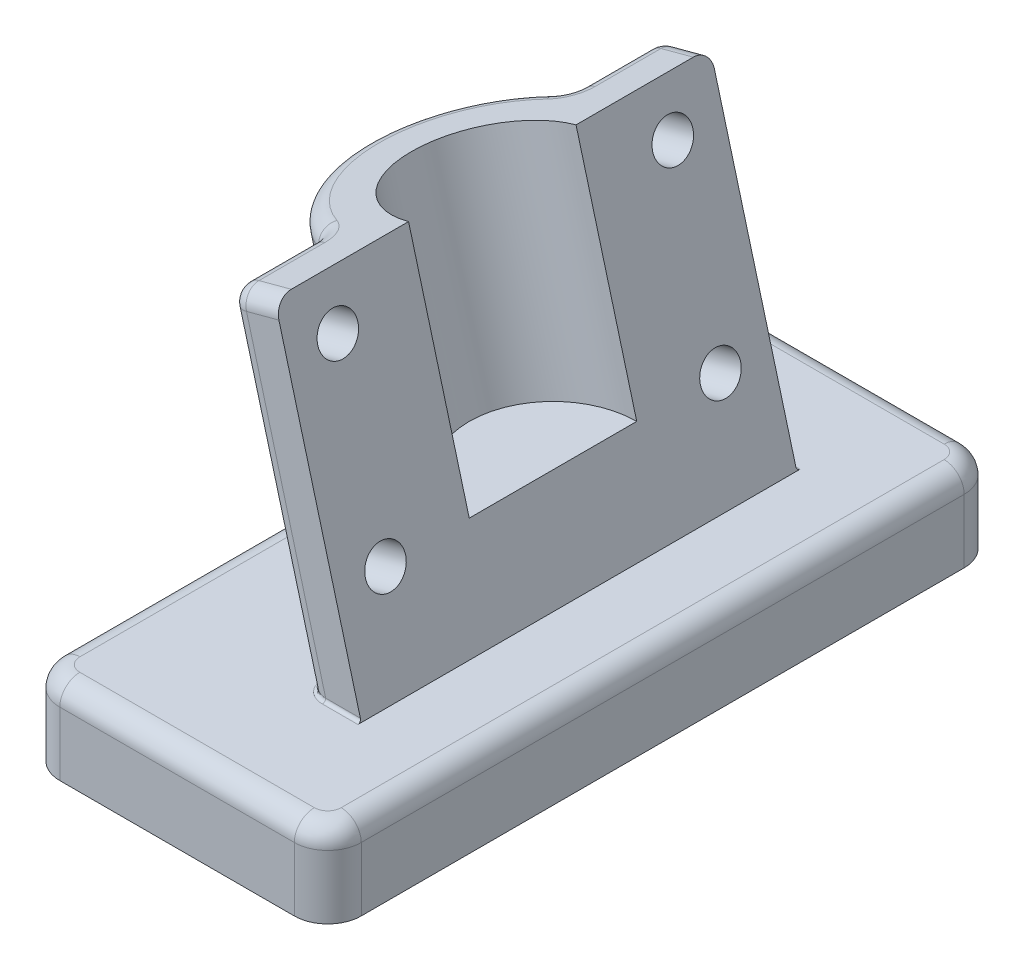
SolidWorks part; units mm, degrees
ref_plane "Front Plane" through (0, 0, 0) normal (0, 0, 1) x (1, 0, 0)
ref_plane "Top Plane" through (0, 0, 0) normal (0, 1, 0) x (1, 0, 0)
ref_plane "Right Plane" through (0, 0, 0) normal (1, 0, 0) x (0, 0, -1)
sketch "Sketch1" plane through (0, 0, 0) normal (0, 1, 0) x (1, 0, 0)
  line L1 (-45, 100) -> (45, 100)
  line L2 (-45, 100) -> (-45, -100)
  line L3 (-45, -100) -> (45, -100)
  line L4 (45, 100) -> (45, -100)
  line L5 (-45, 100) -> (45, -100) construction
  line L6 (-45, -100) -> (45, 100) construction
  point P0 (0, 0)
  dimension "D1" = 90
  dimension "D2" = 200
extrude "Boss-Extrude1" add sketch "Sketch1" along normal blind 25 contours L2 L3 L4 L1
sketch "Sketch3" plane through (0, 0, 0) normal (0, 0, 1) x (1, 0, 0)
  line L0 (-21.411, 25) -> (-44.5189, 111.2398)
  line L1 (-45, 25) -> (45, 25) construction
  line L2 (-44.5189, 111.2398) -> (-5.8819, 121.5926)
  line L3 (-5.8819, 121.5926) -> (20, 25)
  line L4 (45, 25) -> (45, 0) construction
  line L5 (-21.411, 25) -> (20, 25)
  point P8 (20, 25)
  point P9 (-20.9089, 25)
  dimension "D1" = 25
  dimension "D2" = 40
  dimension "D3" = 100
  dimension "D4" = 75
extrude "Boss-Extrude2" add sketch "Sketch3" along normal mid plane 130
sketch "Sketch4" plane through (-30.7922, 114.9179, 0) normal (-0.2588, 0.9659, 0) x (0.9659, 0.2588, 0)
  line L0 (25.789, -65) -> (25.789, 65) construction
  line L2 (25.789, 0) -> (-14.211, 0) construction
  line L8 (10.789, 65) -> (10.789, 37.081)
  line L9 (25.789, 65) -> (-14.211, 65) construction
  line L12 (10.789, 65) -> (-14.211, 65)
  line L13 (-14.211, 65) -> (-14.211, 0)
  arc A0 (10.789, 37.081) -> (-14.211, 0) centre (25.789, 0) ccw
  dimension "D1" = 15
extrude "Cut-Extrude2" cut sketch "Sketch4" against normal up to surface (95.9808 mm away)
mirror "Mirror1" about plane through (0, 0, 0) normal (0, 0, 1) of "Cut-Extrude2"
sketch "Sketch6" plane through (-30.7922, 114.9179, 0) normal (-0.2588, 0.9659, 0) x (0.9659, 0.2588, 0)
  line L0 (25.789, -65) -> (25.789, 65) construction
  line L1 (25.789, 0) -> (25.789, 25) construction
  line L2 (25.789, 0) -> (25.789, -25) construction
  line L3 (25.789, 25) -> (25.789, -25)
  arc A0 (25.789, 25) -> (25.789, -25) centre (25.789, 0) ccw
  dimension "D1" = 50
sketch "Sketch7" plane through (24.9103, 6.6747, 0) normal (0.9659, 0.2588, 0) x (0, 0, -1)
  line L0 (-65, 48.9718) -> (65, 48.9718) construction
  line L1 (-65, 18.9718) -> (-65, 118.9718) construction
  line L2 (65, 18.9718) -> (65, 118.9718) construction
  line L3 (-65, 118.9718) -> (65, 118.9718) construction
  dimension "D1" = 70
ref_plane "Plane2" through (0, 53.9778, 0) normal (0, 1, 0) x (1, 0, 0)
sketch "Sketch8" plane through (0, 53.9778, 0) normal (0, 1, 0) x (1, 0, 0)
  line L0 (12.2354, -65) -> (12.2354, 65) construction
  line L1 (12.2354, 25) -> (12.2354, -25)
  arc A0 (12.2354, 25) -> (12.2354, -25) centre (12.2354, 0) ccw
  dimension "D1" = 50
loft "Cut-Loft1" cut profiles "Sketch6", "Sketch8"
sketch "Sketch9" plane through (24.9103, 6.6747, 0) normal (0.9659, 0.2588, 0) x (0, 0, -1)
  line L0 (25, 118.9718) -> (65, 118.9718) construction
  circle A0 centre (-50, 103.9718) radius 6
  circle A1 centre (50, 103.9718) radius 6
  circle A2 centre (50, 48.9718) radius 6
  circle A3 centre (-50, 48.9718) radius 6
  point P10 (0, 0)
  point P11 (0, 0)
  point P12 (0, 0)
  point P13 (0, 0)
  point P16 (9.5996, 116.6778)
  dimension "D1" = 12
  dimension "D2" = 12
  dimension "D3" = 12
  dimension "D4" = 12
  dimension "D5" = 55
  dimension "D6" = 15
  dimension "D7" = 100
  dimension "D8" = 50
extrude "Cut-Extrude4" cut sketch "Sketch9" against normal up to surface (15 mm away) up to face at (-7.95, 71.3551, 51.0405)
fillet "Fillet1" radius 6 4 edges at (0, 25, -100) (-45, 25, 0) (0, 25, 100) (45, 25, 0)
fillet "Fillet2" radius 5 9 edges at (-7.95, 71.3551, 65) (-7.95, 71.3551, -65) (-7.95, 71.3551, -37.081) (-7.95, 71.3551, 37.081) (-13.1263, 119.6514, 65) (-13.1263, 119.6514, -65) (-20.3708, 117.7103, 51.0405) (-20.3708, 117.7103, -51.0405) (-44.5189, 111.2398, 0)
fillet "Fillet3" radius 10 8 edges at (-43.2426, 23.2426, 98.2426) (43.2426, 23.2426, 98.2426) (43.2426, 23.2426, -98.2426) (-43.2426, 23.2426, -98.2426) (-45, 9.5, -100) (45, 9.5, -100) (45, 9.5, 100) (-45, 9.5, 100)
fillet "Fillet4" radius 1 9 edges at (4.4709, 25, 50.1556) (4.4709, 25, -50.1556) (-21.411, 25, 0) (14.8236, 25, 65) (14.8236, 25, -65) (3.6936, 25, 37.6761) (3.6936, 25, -37.6761) (5.987, 25, 63.5355) (5.987, 25, -63.5355)
